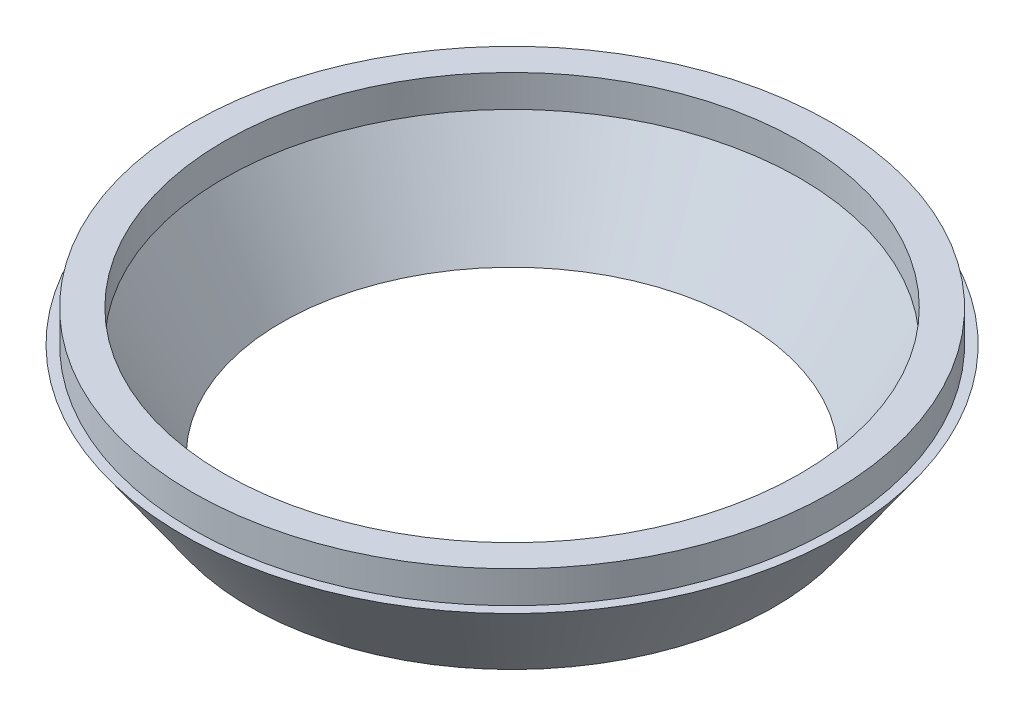
SolidWorks part; units mm, degrees
ref_plane "Front Plane" through (0, 0, 0) normal (0, 0, 1) x (1, 0, 0)
ref_plane "Top Plane" through (0, 0, 0) normal (0, 1, 0) x (1, 0, 0)
ref_plane "Right Plane" through (0, 0, 0) normal (1, 0, 0) x (0, 0, -1)
sketch "Sketch2" plane through (0, 0, 0) normal (0, 0, 1) x (1, 0, 0)
  line L0 (0, 0) -> (0, 19.05) construction
  line L1 (-45.72, 0) -> (-52.07, 0)
  line L2 (-57.15, 19.05) -> (-65.405, 19.05)
  line L3 (-65.405, 19.05) -> (-52.07, 0)
  line L4 (-57.15, 19.05) -> (-45.72, 0)
  dimension "D1" = 65.405
  dimension "D2" = 57.15
  dimension "D3" = 45.72
  dimension "D4" = 52.07
  dimension "D5" = 19.05
revolve "Revolve1" add sketch "Sketch2" angle 360 about L0
sketch "Sketch3" plane through (0, 19.05, 0) normal (0, 1, 0) x (1, 0, 0)
  circle A0 centre (0, 0) radius 57.15
  circle A1 centre (0, 0) radius 63.5
  dimension "D1" = 114.3
  dimension "D2" = 127
extrude "Boss-Extrude1" add sketch "Sketch3" along normal blind 6.35
equation "\"Inside Diamter\"= 5in"
equation "\"Inside Thickness\"= 0.5in"
equation "\"D2@Sketch2\"=(\"Inside Diamter\" - \"Inside Thickness\")/2"
equation "\"Bottom Diameter\"= 3.6"
equation "\"D3@Sketch2\" = \"Bottom Diameter\" / 2"
equation "\"D4@Sketch2\"= ( \"Bottom Diameter\" + \"Inside Thickness\" ) / 2"
equation "\"D1@Sketch3\"=\"Inside Diamter\"-\"Inside Thickness\""
equation "\"D2@Sketch3\"=\"Inside Diamter\""
